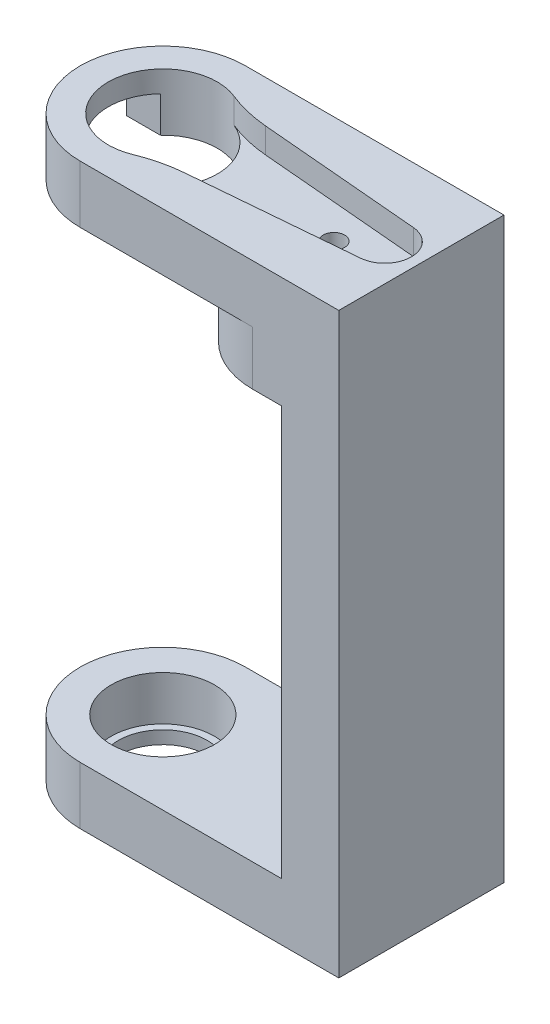
SolidWorks part; units mm, degrees
ref_plane "Front Plane" through (0, 0, 0) normal (0, 0, 1) x (1, 0, 0)
ref_plane "Top Plane" through (0, 0, 0) normal (0, 1, 0) x (1, 0, 0)
ref_plane "Right Plane" through (0, 0, 0) normal (1, 0, 0) x (0, 0, -1)
sketch "Sketch1" plane through (0, 0, 0) normal (0, 1, 0) x (1, 0, 0)
  circle A0 centre (0, 0) radius 3.8
  circle A1 centre (0, 0) radius 5.75
  dimension "D1" = 7.6
  dimension "D2" = 11.5
extrude "Boss-Extrude1" add sketch "Sketch1" against normal blind 2.25
sketch "Sketch2" plane through (0, 0, 0) normal (0, 1, 0) x (1, 0, 0)
  line L0 (0, 5.75) -> (18, 5.75)
  line L1 (18, 5.75) -> (18, -5.75)
  line L2 (18, -5.75) -> (0, -5.75)
  line L3 (0, -5.75) -> (0, 5.75) construction
  circle A0 centre (0, 0) radius 5.75 construction
  circle A2 centre (0, 0) radius 5.75
  arc A3 (0, -5.75) -> (0, 5.75) centre (0, 0) ccw
  dimension "D1" = 18
  dimension "D2" = 0
extrude "Boss-Extrude2" add sketch "Sketch2" against normal up to surface (2.25 mm away) up to face at (0, -2.25, 3.8)
sketch "Sketch3" plane through (0, -2.25, 0) normal (0, -1, 0) x (1, 0, 0)
  line L0 (18, -5.75) -> (18, 5.75) construction
  line L1 (18, 5.75) -> (6.25, 5.75)
  line L2 (18, 5.75) -> (18, -5.75)
  line L3 (18, -5.75) -> (6.25, -5.75)
  line L5 (6.25, 5.75) -> (6.25, -5.75)
  line L9 (0, -5.75) -> (18, -5.75) construction
  line L10 (18, 5.75) -> (0, 5.75) construction
  arc A1 (0, 5.75) -> (0, -5.75) centre (0, 0) ccw construction
  point P9 (-5.75, 0)
  dimension "D1" = 12
extrude "Boss-Extrude3" add sketch "Sketch3" along normal blind 5.75 contours L2 L1 L5 L3
sketch "Sketch4" plane through (0, 0, 0) normal (0, 1, 0) x (1, 0, 0)
  line L0 (2.3362, -2.997) -> (15.6102, -1.843)
  line L1 (15.6102, 1.843) -> (2.3362, 2.997)
  line L2 (0, 0) -> (15.45, 0) construction
  line L4 (2.2978, -2.9) -> (15.6016, -1.7434) construction
  line L5 (15.6016, 1.7434) -> (2.2978, 2.9) construction
  line L7 (0, -5.75) -> (18, -5.75)
  line L8 (18, -5.75) -> (18, 5.75)
  line L9 (18, 5.75) -> (0, 5.75)
  line L10 (0, -5.75) -> (18, -5.75)
  line L11 (18, -5.75) -> (18, 5.75)
  line L12 (18, 5.75) -> (0, 5.75)
  arc A0 (15.6102, -1.843) -> (15.6102, 1.843) centre (15.45, 0) ccw
  arc A1 (2.3362, 2.997) -> (2.3362, -2.997) centre (0, 0) ccw
  arc A4 (0, 5.75) -> (0, -5.75) centre (0, 0) ccw
  arc A5 (0, 5.75) -> (0, -5.75) centre (0, 0) ccw
  arc A6 (15.6016, -1.7434) -> (15.6016, 1.7434) centre (15.45, 0) ccw construction
  arc A7 (2.2978, 2.9) -> (2.2978, -2.9) centre (0, 0) ccw construction
  circle M15 centre (0, 0) radius 3.8
  arc M16 (0, 5.75) -> (0, -5.75) centre (0, 0) ccw
  line M17 (0, -5.75) -> (18, -5.75)
  line M18 (18, -5.75) -> (18, 5.75)
  line M19 (18, 5.75) -> (0, 5.75)
  dimension "D2" = 3.7
  dimension "D3" = 1.75
  dimension "D4" = 15.45
  dimension "D5" = 0.1
  dimension "D6" = 5.8
  dimension "D1" = 0
extrude "Boss-Extrude4" add sketch "Sketch4" along normal blind 1.75 contours L1 L0 M18 M19 M16 M17 M15 region at (-5.4861, 0, 0)
fillet "Fillet3" radius 10 2 edges at (2.3362, 0.875, 2.997) (2.3362, 0.875, -2.997)
sketch "Sketch6" plane through (0, 0, 0) normal (1, 0, 0) x (0, 0, -1)
  line L1 (2.6, 0.25) -> (-2.6, 0.25)
  line L2 (5.75, 1.75) -> (-5.75, 1.75) construction
  line L3 (2.6, 0.25) -> (2.6, -2.25)
  line L4 (-5.75, -2.25) -> (5.75, -2.25) construction
  line L5 (2.6, -2.25) -> (-2.6, -2.25)
  line L6 (-2.6, -2.25) -> (-2.6, 0.25)
  line L7 (0, 0) -> (0, -2.25) construction
  point P10 (0, 0)
  dimension "D1" = 1.5
  dimension "D2" = 5.2
extrude "Cut-Extrude1" cut sketch "Sketch6" against normal through all
sketch "Sketch7" plane through (0, 0, 0) normal (0, 1, 0) x (1, 0, 0)
  line L0 (11.91, 0) -> (0, 0) construction
  circle A0 centre (11.91, 0) radius 0.75
  dimension "D1" = 11.91
  dimension "D2" = 1.5
extrude "Cut-Extrude2" cut sketch "Sketch7" against normal through all
fillet "Fillet1" 2 edges at (6.25, -5.125, -5.75) (6.25, -5.125, 5.75) type full round first side face at (8.0833, -2.8333, -5.75) second side face at (8.0833, -2.8333, 5.75) middle face at (6.25, -5.125, 0)
sketch "Sketch5" plane through (0, -8, 0) normal (0, -1, 0) x (1, 0, 0)
  line L0 (18, 5.75) -> (12, 5.75) construction
  line L1 (14, 5.75) -> (18, 5.75)
  line L2 (14, 5.75) -> (14, -5.75)
  line L3 (14, -5.75) -> (18, -5.75)
  line L4 (18, 5.75) -> (18, -5.75)
  line L5 (12, -5.75) -> (18, -5.75) construction
  point P8 (0, 0)
  dimension "D1" = 14
  dimension "D2" = 4
extrude "Boss-Extrude5" add sketch "Sketch5" along normal blind 26.5 and the other way blind 4
chamfer "Chamfer1" distance 2 angle 45 3 edges at (13, -8, 5.75) (13, -8, -5.75) (6.25, -8, 0)
sketch "Sketch8" plane through (0, -34.5, 0) normal (0, -1, 0) x (1, 0, 0)
  line L0 (18, 5.75) -> (0, 5.75)
  line L1 (18, -5.75) -> (18, 5.75) construction
  line L2 (18, 5.75) -> (14, 5.75) construction
  line L3 (0, -5.75) -> (18, -5.75)
  line L4 (14, -5.75) -> (18, -5.75) construction
  line L5 (18, 5.75) -> (18, -5.75)
  arc A0 (0, 5.75) -> (0, -5.75) centre (0, 0) ccw
  circle A1 centre (0, 0) radius 3.6
  dimension "D1" = 7.2
extrude "Boss-Extrude6" add sketch "Sketch8" along normal blind 4
sketch "Sketch9" plane through (0, -38.5, 0) normal (0, -1, 0) x (1, 0, 0)
  circle A0 centre (0, 0) radius 3.6 construction
  circle A1 centre (0, 0) radius 3.6
  circle A2 centre (0, 0) radius 3.1
  dimension "D1" = 0.5
extrude "Boss-Extrude7" add sketch "Sketch9" against normal blind 0.9
